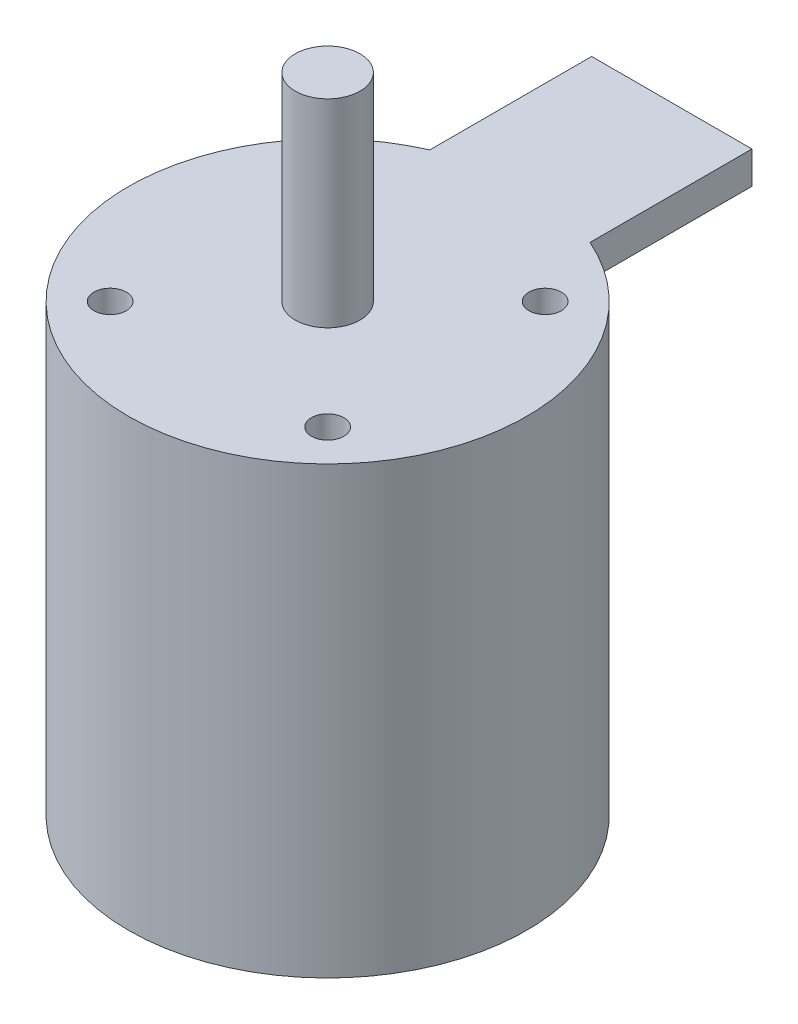
SolidWorks part; units mm, degrees
ref_plane "Front Plane" through (0, 0, 0) normal (0, 0, 1) x (1, 0, 0)
ref_plane "Top Plane" through (0, 0, 0) normal (0, 1, 0) x (1, 0, 0)
ref_plane "Right Plane" through (0, 0, 0) normal (1, 0, 0) x (0, 0, -1)
sketch "Sketch1" plane through (0, 0, 0) normal (0, 1, 0) x (1, 0, 0)
  circle A0 centre (0, 0) radius 24.6
  dimension "D1" = 49.2
extrude "Boss-Extrude1" add sketch "Sketch1" along normal blind 55
sketch "Sketch2" plane through (0, 55, 0) normal (0, 1, 0) x (1, 0, 0)
  circle A0 centre (0, 0) radius 4
  dimension "D1" = 8
extrude "Boss-Extrude2" add sketch "Sketch2" along normal blind 24.5
sketch "Sketch3" plane through (0, 55, 0) normal (0, -1, 0) x (1, 0, 0)
  line L0 (0, 0) -> (0, -45.0413) construction
  line L1 (-9.8984, -22.5207) -> (9.8984, -22.5207)
  line L2 (-9.8984, -22.5207) -> (-9.8984, -42.5207)
  line L3 (-9.8984, -42.5207) -> (9.8984, -42.5207)
  line L4 (9.8984, -22.5207) -> (9.8984, -42.5207)
  circle A0 centre (0, 0) radius 24.6 construction
  point P7 (0, 0)
  point P8 (0, 0)
  point P11 (0, -22.5207)
  dimension "D1" = 20
sketch "Sketch4" plane through (0, 55, 0) normal (0, 1, 0) x (1, 0, 0)
  line L0 (0, 0) -> (-30.91, 30.91) construction
  line L1 (0, 0) -> (-36.9113, 0) construction
  circle A0 centre (-13.435, 13.435) radius 2
  circle A1 centre (13.435, 13.435) radius 2
  circle A2 centre (13.435, -13.435) radius 2
  circle A3 centre (-13.435, -13.435) radius 2
  point P15 (0, 0)
  dimension "D2" = 4
  dimension "D1" = 45
  dimension "D3" = 19
  dimension "D4" = 4
extrude "Cut-Extrude1" cut sketch "Sketch4" against normal blind 5
extrude "Boss-Extrude4" add sketch "Sketch3" along normal blind 4
